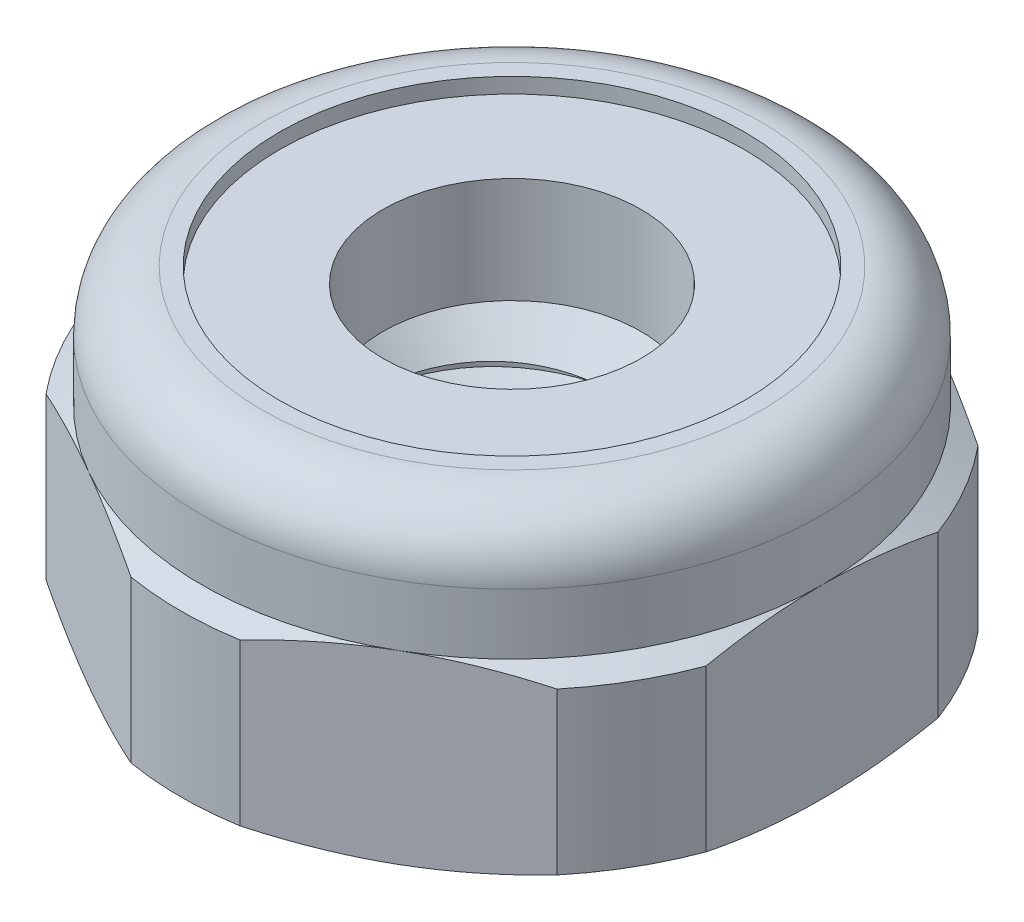
SolidWorks part; units mm, degrees
ref_plane "Front Plane" through (0, 0, 0) normal (0, 0, 1) x (1, 0, 0)
ref_plane "Top Plane" through (0, 0, 0) normal (0, 1, 0) x (1, 0, 0)
ref_plane "Right Plane" through (0, 0, 0) normal (1, 0, 0) x (0, 0, -1)
sketch "Sketch1" plane through (0, 0, 0) normal (1, 0, 0) x (0, 0, -1)
  line L0 (0, -1.5748) -> (0, 1.5748) construction
  line L1 (-1.4224, 1.5748) -> (1.4224, 1.5748) construction
  line L2 (-3.1877, 1.5748) -> (3.1877, 1.5748) construction
  line L3 (1.4911, 2.1701) -> (0.9412, 1.8526) construction
  line L4 (0.9412, 1.8526) -> (1.4911, 1.5351) construction
  line L5 (1.4911, 1.5351) -> (1.4911, 2.1701) construction
  line L6 (1.4224, 2.1304) -> (1.4224, 1.5748) construction
  line L7 (1.4911, 1.8526) -> (1.4224, 1.8526) construction
  line L8 (1.4224, 1.8526) -> (1.01, 1.8526) construction
  line L9 (1.01, 1.8526) -> (0.9412, 1.8526) construction
  line L10 (1.01, 1.8923) -> (1.01, 1.8129)
  line L11 (1.4568, 2.1503) -> (1.4568, 1.555)
  line L12 (1.01, 1.8129) -> (1.4568, 1.555)
  line L13 (1.01, 1.8923) -> (1.4568, 2.1503)
  point P3 (-1.01, 1.8526)
  point P9 (0, 0.3302)
  point P20 (1.4568, 1.8526)
  point P21 (1.01, 1.8526)
  point P22 (3.4036, 1.5748)
  dimension "Height (A)" = 3.1496
  dimension "Thread Dia" = 2.8448
  dimension "Width (B)" = 6.3754
  dimension "Wrench Pad (D)" = 1.905
  dimension "Thread Pitch" = 0.635
  dimension "D2" = 0.0794
  dimension "Across Corners (C)" = 6.8072
sketch "Sketch2" plane through (0, 0, 0) normal (0, 1, 0) x (1, 0, 0)
  line L1 (3.1877, 1.8404) -> (0, 3.6808)
  line L2 (0, 3.6808) -> (-3.1877, 1.8404)
  line L3 (-3.1877, 1.8404) -> (-3.1877, -1.8404)
  line L4 (-3.1877, -1.8404) -> (0, -3.6808)
  line L5 (0, -3.6808) -> (3.1877, -1.8404)
  line L6 (3.1877, -1.8404) -> (3.1877, 1.8404)
  circle A0 centre (0, 0) radius 3.1877 construction
  circle A1 centre (0, 0) radius 1.4224
extrude "Boss-Extrude1" add sketch "Sketch2" against normal up to vertex (1.5748 mm away) from vertex up to point (0, -1.5748, 0) starting at point (0, 0.3302, 0)
sketch "Sketch3" plane through (0, 0.3302, 0) normal (0, 1, 0) x (1, 0, 0)
  line L0 (3.1877, -1.8404) -> (3.1877, 1.8404) construction
  circle A0 centre (0, 0) radius 3.1877
  circle A1 centre (0, 0) radius 2.3908
  dimension "D1" = 4.7816
extrude "Boss-Extrude2" add sketch "Sketch3" along normal up to vertex (1.2446 mm away) up to point (0, 1.5748, 0)
sketch "Sketch4" plane through (0, 0.3302, 0) normal (0, 1, 0) x (1, 0, 0)
  circle A0 centre (0, 0) radius 3.4036
extrude "Cut-Extrude1" cut sketch "Sketch4" against normal through all flip side to cut
sketch "Sketch7" plane through (0, 0.3302, 0) normal (0, 1, 0) x (1, 0, 0)
  circle A0 centre (0, 0) radius 3.1877 construction
  circle A1 centre (0, 0) radius 3.1877
extrude "Cut-Extrude2" cut sketch "Sketch7" against normal through all draft 60 flip side to cut
extrude "Cut-Extrude3" cut sketch "Sketch7<2>" along normal through all draft 60 from surface flip side to cut starting at face at (0, -1.5748, 1.4224)
sketch "Sketch7<2>" plane through (0, 0.3302, 0) normal (0, 1, 0) x (1, 0, 0) same geometry as "Sketch7"
sketch "Sketch8" plane through (0, 0.3302, 0) normal (0, 1, 0) x (1, 0, 0)
  circle A0 centre (0, 0) radius 2.6448
  circle A1 centre (0, 0) radius 2.3908 construction
  circle A2 centre (0, 0) radius 1.3275
  point P6 (0, 1.01)
  point P9 (0, 1.3275)
  dimension "D2" = 0.3175
extrude "Boss-Extrude3" add sketch "Sketch8" along normal offset from surface (1.0871 mm away) 0.1575 separate body up to face at (0, 1.5748, 3.1877)
sketch "Sketch10" plane through (0, 0.3302, 0) normal (0, 1, 0) x (1, 0, 0)
  circle A0 centre (0, 0) radius 2.6448 construction
  circle A1 centre (0, 0) radius 2.6448
extrude "Cut-Extrude4" cut sketch "Sketch10" along normal offset from surface (1.0871 mm away) 0.1575 up to face at (0, 1.5748, 3.1877)
chamfer "Chamfer1" distance 0.1588 angle 45 2 edges at (0, -1.5748, 1.4224) (0, 0.3302, 1.4224)
fillet "Fillet1" radius 0.6223 1 edges at (0, 1.5748, 3.1877)
sketch "Sketch11" plane through (0, 1.5748, 0) normal (0, 1, 0) x (1, 0, 0)
  circle A0 centre (0, 0) radius 1.4224 construction
  circle A1 centre (0, 0) radius 1.4224
curve "Helix/Spiral1" pitch 0.635 height 3.7846 radius 1.4224 centre (0, 1.5748, 0) axis (0, -1, 0) start towards (0, 0, -1)
sketch "Sketch12" plane through (0, 0, 0) normal (1, 0, 0) x (0, 0, -1)
  line L0 (1.01, 1.8923) -> (1.01, 1.8129) construction
  line L1 (1.01, 1.8129) -> (1.4568, 1.555) construction
  line L2 (1.4568, 2.1503) -> (1.4568, 1.555) construction
  line L3 (1.01, 1.8923) -> (1.4568, 2.1503) construction
  line L4 (1.01, 1.8923) -> (1.01, 1.8129)
  line L5 (1.01, 1.8129) -> (1.4568, 1.555)
  line L6 (1.4568, 2.1503) -> (1.4568, 1.555)
  line L7 (1.01, 1.8923) -> (1.4568, 2.1503)
sweep "Sweep1" add profiles "Sketch12" path "Helix/Spiral1"
sketch "Sketch13" plane through (0, 0.3302, 0) normal (0, 1, 0) x (1, 0, 0)
  circle A0 centre (0, 0) radius 1.5811 construction
  circle A1 centre (0, 0) radius 1.5811
extrude "Cut-Extrude5" cut sketch "Sketch13" against normal through all draft 45 and the other way through all
extrude "Cut-Extrude6" cut sketch "Sketch13<2>" along normal through all draft 45 and the other way through all from surface starting at face at (0, -1.5748, 1.5811)
sketch "Sketch13<2>" plane through (0, 0.3302, 0) normal (0, 1, 0) x (1, 0, 0) same geometry as "Sketch13"
equation "\"D2@Sketch1\" = \"Thread Pitch@Sketch1\" / 8"
equation "\"D1@Fillet1\" = \"Height (A)@Sketch1\" / 6"
equation "\"D1@Sketch3\" = \"Width (B)@Sketch1\" * .75"
equation "\"D1@Chamfer1\" = \"Thread Pitch@Sketch1\" * .25"
equation "\"D3@Helix/Spiral1\" = \"Height (A)@Sketch1\" + \"Thread Pitch@Sketch1\""
equation "\"D4@Helix/Spiral1\" = \"Thread Pitch@Sketch1\""
equation "\"D2@Sketch8\" = \"Thread Pitch@Sketch1\" / 2"
equation "\"D1@Fillet1\" =  ( \"Height (A)@Sketch1\" - \"Wrench Pad (D)@Sketch1\" )  / 2"
equation "\"D1@Boss-Extrude3\" = \"Height (A)@Sketch1\" / 20"
equation "\"D1@Cut-Extrude4\"=\"height (a)@sketch1\"/20"
